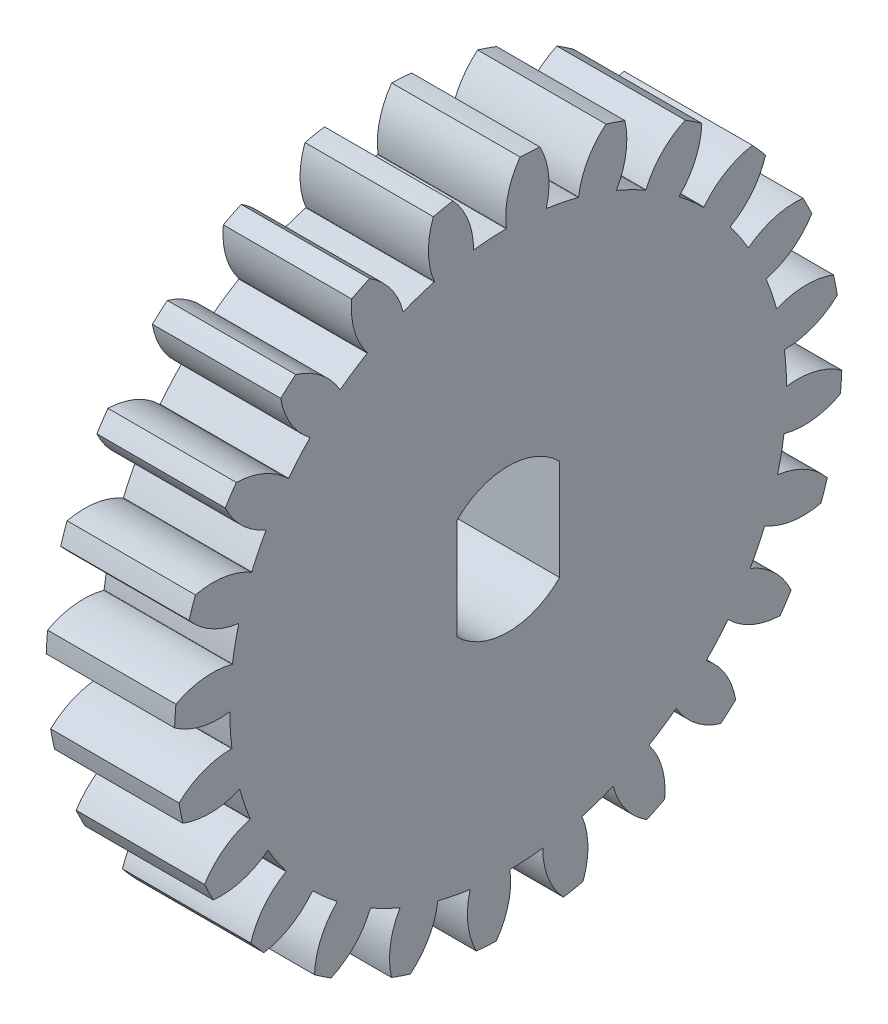
SolidWorks part; units mm, degrees
ref_plane "Front Plane" through (0, 0, 0) normal (0, 0, 1) x (1, 0, 0)
ref_plane "Top Plane" through (0, 0, 0) normal (0, 1, 0) x (1, 0, 0)
ref_plane "Right Plane" through (0, 0, 0) normal (1, 0, 0) x (0, 0, -1)
sketch "Sketch1" plane through (0, 0, 0) normal (1, 0, 0) x (0, 0, -1)
  line L0 (0, 0) -> (0, 13) construction
  line L1 (0, 0) -> (1.6968, 12.8888) construction
  line L2 (-2.9089, 11.2477) -> (0, 12)
  circle A0 centre (0, 0) radius 12 construction
  circle A1 centre (0, 0) radius 13
  circle A2 centre (0, 0) radius 10.843
  circle A3 centre (0, 0) radius 11.6178 construction
  circle A5 centre (2.9044, 11.2489) radius 3
  dimension "D1" = 24
  dimension "D2" = 26
  dimension "D3" = 21.686
  dimension "D6" = 6
  dimension "D4" = 7.5
  dimension "D5" = 75.5
ref_axis "Axis1" through (7.0509, 0, 0) along (-1, 0, 0)
sketch "Sketch2" plane through (0, 0, 0) normal (1, 0, 0) x (0, 0, -1)
  circle A0 centre (0, 0) radius 10.843
  circle A1 centre (0, 0) radius 10.843 construction
extrude "Boss-Extrude1" add sketch "Sketch2" along normal mid plane 5
sketch "Sketch4" plane through (0, 0, 0) normal (1, 0, 0) x (0, 0, -1)
  line L0 (0, 0) -> (0, 13) construction
  line L1 (0, 0) -> (2.1414, 32.6712) construction
  arc A0 (0.8826, 13.4652) -> (0.6106, 9.3154) centre (2.9044, 11.2489) ccw
  circle A1 centre (2.9044, 11.2489) radius 3 construction
  arc A2 (0.8826, 13.4652) -> (0.6106, 9.3154) centre (-1.4113, 11.5317) cw
  dimension "D1" = 3.75
extrude "Boss-Extrude3" add sketch "Sketch4" along normal mid plane 5
sketch "Sketch5" plane through (0, 0, 0) normal (1, 0, 0) x (0, 0, -1)
  circle A0 centre (0, 0) radius 13
  circle A1 centre (0, 0) radius 13 construction
  circle A2 centre (0, 0) radius 38.4
  dimension "D1" = 25.4
extrude "Cut-Extrude1" cut sketch "Sketch5" against normal through all both and the other way through all
fillet "Fillet1" radius 0.01 2 edges at (0, 10.8428, 0.0679) (0, 10.7412, -1.4826)
pattern_circular "CirPattern2" count 24 over 360 about axis through (2.5, 0, 0) along (1, 0, 0) of "Fillet1", "Cut-Extrude1", "Boss-Extrude3"
shell "Shell1" [suppressed] thickness 4.5
sketch "Sketch6" plane through (0, 0, 0) normal (1, 0, 0) x (0, 0, -1)
  circle A0 centre (0, 0) radius 12 construction
  dimension "D1" = 24
sketch "Sketch7" plane through (-2.5, 0, 0) normal (-1, 0, 0) x (0, 0, 1)
  line L0 (-1.9, 1.9183) -> (-1.9, -1.9183) construction
  line L1 (1.9, -1.9183) -> (1.9, 1.9183) construction
  line L2 (-1.9, 0) -> (1.9, 0) construction
  line L3 (-2, 1.9596) -> (-2, -1.9596)
  line L4 (2, -1.9596) -> (2, 1.9596)
  arc A0 (-1.9, -1.9183) -> (1.9, -1.9183) centre (0, 0) ccw construction
  arc A1 (1.9, 1.9183) -> (-1.9, 1.9183) centre (0, 0) ccw construction
  arc A2 (2, 1.9596) -> (-2, 1.9596) centre (0, 0) ccw
  arc A3 (-2, -1.9596) -> (2, -1.9596) centre (0, 0) ccw
  point P9 (0, 0)
  dimension "D1" = 5.4
  dimension "D2" = 3.8
  dimension "D3" = 0.1
extrude "Cut-Extrude2" cut sketch "Sketch7" against normal through all
equation "\"N\"= 24"
equation "\"DP\"= 1"
equation "\"PD\"= \"N\" / \"DP\""
equation "\"CP\"= \"PD\" / \"N\" * 3.141"
equation "\"A\"= 1 / \"DP\""
equation "\"D\"= 1.157 / \"DP\""
equation "\"OD\"= \"PD\" + 2 * \"A\""
equation "\"RD\"= \"PD\" - 2 * \"D\""
equation "\"T\"= 5"
equation "\"F\"= .01"
equation "\"D1@Sketch1\"=\"PD\""
equation "\"D1@Boss-Extrude1\"=\"T\""
equation "\"D4@Sketch1\"=360/(\"N\"*2)"
equation "\"D6@Sketch1\"=\"PD\"/4"
equation "\"D3@Sketch1\"=\"RD\""
equation "\"D2@Sketch1\"=\"OD\""
equation "\"D1@Sketch4\"=360/(\"N\"*4)"
equation "\"D1@Boss-Extrude3\"=\"T\""
equation "\"D1@Fillet1\"=\"F\""
equation "\"D1@CirPattern2\"=\"N\""
equation "\"D1@Shell1\"=\"T\"*.9"
equation "\"D1@Sketch6\"=\"PD\""
